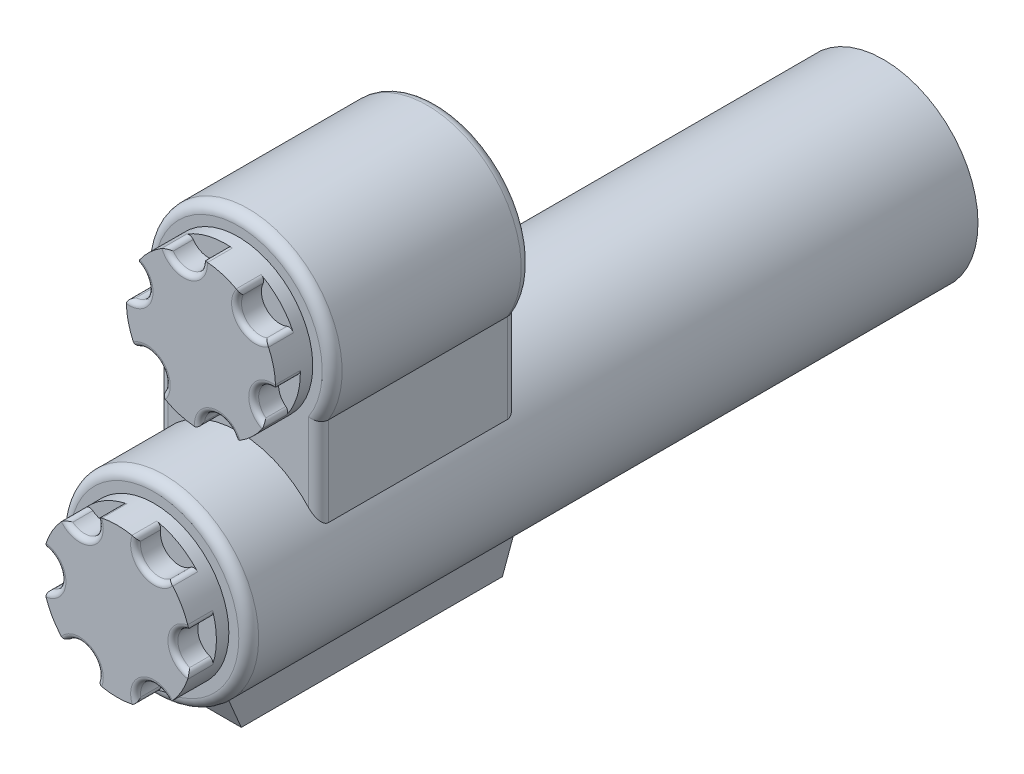
SolidWorks part; units mm, degrees
material "PET"
ref_plane "Front Plane" through (0, 0, 0) normal (0, 0, 1) x (1, 0, 0)
ref_plane "Top Plane" through (0, 0, 0) normal (0, 1, 0) x (1, 0, 0)
ref_plane "Right Plane" through (0, 0, 0) normal (1, 0, 0) x (0, 0, -1)
sketch "Sketch2" plane through (0, 0, 0) normal (0, 0, 1) x (1, 0, 0)
  circle A2 centre (325.6373, 52.475) radius 18.9484
  circle A3 centre (325.6373, 52.475) radius 18.9484
  dimension "D1" = 1.27
extrude "Boss-Extrude1" add sketch "Sketch2" against normal blind 12.7
sketch "Sketch3" plane through (0, 0, 0) normal (0, 0, 1) x (1, 0, 0)
  circle A0 centre (325.6373, 52.475) radius 24.13 construction
  circle A1 centre (325.6373, 52.475) radius 24.13
extrude "Boss-Extrude2" add sketch "Sketch3" along normal blind 76.2
sketch "Sketch4" plane through (0, 0, 76.2) normal (0, 0, 1) x (1, 0, 0)
  circle A0 centre (325.6373, 52.475) radius 19.05
  dimension "D1" = 38.1
extrude "Boss-Extrude3" add sketch "Sketch4" along normal blind 9.525
sketch "Sketch5" plane through (0, 0, 85.725) normal (0, 0, 1) x (1, 0, 0)
  line L0 (325.6373, 52.475) -> (344.6873, 52.475) construction
  circle A0 centre (325.6373, 52.475) radius 19.05 construction
  circle A1 centre (344.6873, 52.475) radius 4.7625
  dimension "D1" = 9.525
extrude "Cut-Extrude1" cut sketch "Sketch5" against normal blind 6.35
fillet "Fillet1" radius 1.27 3 edges at (344.092, 57.2001, 82.55) (339.9248, 52.475, 85.725) (344.092, 47.7499, 82.55)
pattern_circular "CirPattern1" count 6 over 360 about axis through (325.6373, 52.475, 85.725) along (0, 0, -1) of "Cut-Extrude1", "Fillet1" reverse direction yes
chamfer "Chamfer1" distance 2.54 angle 45 1 edges at (344.5857, 52.475, -12.7)
sketch "Sketch6" plane through (-0.0014, 0, 3.7009) normal (0.0004, 0, -1) x (-1, 0, -0.0004)
  circle A0 centre (-325.5233, 100.6049) radius 24
  ellipse E0 centre (-325.6373, 52.475) end of major axis (-325.6373, 76.605) minor radius 24.13 construction
  dimension "D1" = 48.1299
extrude "Boss-Extrude4" add sketch "Sketch6" against normal blind 50.8 separate body
sketch "Sketch7" plane through (-0.0014, 0, 3.7009) normal (0.0004, 0, -1) x (-1, 0, -0.0004)
  line L0 (-346.0236, 87.995) -> (-346.0236, 64.955) construction
  line L1 (-305.0236, 65.3846) -> (-346.0236, 65.3846)
  line L2 (-305.0236, 65.3846) -> (-305.0236, 88.1244)
  line L4 (-346.0236, 65.3846) -> (-346.0236, 88.1254)
  line L5 (-305.0236, 64.955) -> (-305.0236, 87.995) construction
  circle A0 centre (-325.5233, 100.6049) radius 24 construction
  arc A1 (-346.0236, 88.1254) -> (-305.0236, 88.1244) centre (-325.5233, 100.6049) ccw
  ellipse E1 centre (-325.6373, 52.475) end of major axis (-325.6373, 76.605) minor radius 24.13 construction
  circle M6 centre (-325.5233, 100.6049) radius 24
extrude "Boss-Extrude5" add sketch "Sketch7" against normal up to surface (50.8 mm away) contours L4 M6 | L1 L2 A1 region at (325.5223, 73.0425, 3.8219) up to face at (301.503, 100.6049, 54.613)
sketch "Sketch8" plane through (-0.0202, 0, 54.5009) normal (-0.0004, 0, 1) x (1, 0, 0.0004)
  circle A0 centre (325.5233, 100.6049) radius 19.05
  dimension "D1" = 38.1
extrude "Boss-Extrude6" add sketch "Sketch8" along normal blind 9.525
sketch "Sketch9" plane through (-0.0238, 0, 64.0259) normal (-0.0004, 0, 1) x (1, 0, 0.0004)
  line L0 (325.5233, 100.6049) -> (343.7707, 95.1338) construction
  circle A0 centre (325.5233, 100.6049) radius 19.05 construction
  circle A1 centre (343.7707, 95.1338) radius 4.7625
  dimension "D1" = 9.525
extrude "Cut-Extrude2" cut sketch "Sketch9" against normal blind 6.35
fillet "Fillet2" radius 1.27 3 edges at (344.5349, 99.8309, 60.9789) (339.1851, 96.5016, 64.152) (341.8208, 90.7787, 60.9779)
pattern_circular "CirPattern2" count 6 over 360 about axis through (325.4995, 100.6049, 64.1469) along (0.0004, 0, -1) of "Cut-Extrude2", "Fillet2" reverse direction yes
fillet "Fillet3" radius 2.54 7 edges at (349.7673, 52.475, 76.2) (346.0033, 76.771, 54.6295) (325.5024, 124.6049, 54.6219) (305.0033, 76.7545, 54.6143) (346.0222, 76.7561, 3.8295) (325.5213, 124.6049, 3.8219) (305.0222, 76.7545, 3.8143)
ref_axis "Axis1" through (325.6373, 52.475, 73.66) along (0, 0, -1)
ref_plane "Plane1" through (325.6373, 0, 0) normal (1, 0, 0) x (0, 0, -1)
sketch "Sketch10" plane through (0, 0, 0) normal (0, 0, -1) x (-1, 0, 0)
  line L0 (-325.6373, 40.513) -> (-325.6373, -40.513) construction
  line L1 (-312.9373, 23.5825) -> (-338.3373, 23.5825)
  line L2 (-312.9373, 23.5825) -> (-312.9373, 33.1075)
  line L3 (-312.9373, 33.1075) -> (-338.3373, 33.1075)
  line L4 (-338.3373, 23.5825) -> (-338.3373, 33.1075)
  line L5 (-312.9373, 23.5825) -> (-338.3373, 33.1075) construction
  line L6 (-312.9373, 33.1075) -> (-338.3373, 23.5825) construction
  circle A0 centre (-325.6373, 52.475) radius 24.13 construction
  point P0 (-325.6373, 28.345)
  dimension "D1" = 4.7625
  dimension "D2" = 25.4
extrude "Boss-Extrude7" add sketch "Sketch10" against normal offset from surface (66.675 mm away) 9.525 up to face at (347.2273, 52.475, 76.2)
draft "Draft2" type of draft neutral plane draft angle 30 faces to draft 1 face at (325.6373, 26.8669, 66.675) neutral plane through (312.9373, 23.5825, 103.3272) neutral plane normal (0, -1, 0) parameters "D1"=30
draft "Draft3" type of draft neutral plane draft angle 15 faces to draft 1 face at (312.9373, 27.77, 34.5463) neutral plane through (312.9373, 23.5825, 103.3272) neutral plane normal (0, -1, 0) parameters "D1"=15
draft "Draft4" type of draft neutral plane draft angle 15 faces to draft 1 face at (338.3373, 27.77, 34.5463) neutral plane through (312.9373, 23.5825, 103.3272) neutral plane normal (0, -1, 0) parameters "D1"=15
sketch "Sketch11" plane through (0, 0, 0) normal (0, 0, -1) x (-1, 0, 0)
  circle A0 centre (-325.6373, 52.475) radius 18.9484 construction
  circle A1 centre (-325.6373, 52.475) radius 18.9484
extrude "Cut-Extrude4" cut sketch "Sketch11" against normal offset from surface 19.05 and the other way up to next up to face at (325.6373, 52.475, 85.725)
sketch "Sketch12" plane through (0, 0, 0) normal (0, 0, -1) x (-1, 0, 0)
  arc A0 (-310.1548, 33.9669) -> (-341.1198, 33.9669) centre (-325.6373, 52.475) ccw construction
  circle A1 centre (-325.6373, 52.475) radius 18.9484 construction
  circle A2 centre (-325.6373, 52.475) radius 24.13
  circle A3 centre (-325.6373, 52.475) radius 18.9484
  point P6 (-310.3731, 33.1522)
extrude "Boss-Extrude8" add sketch "Sketch12" along normal blind 110
